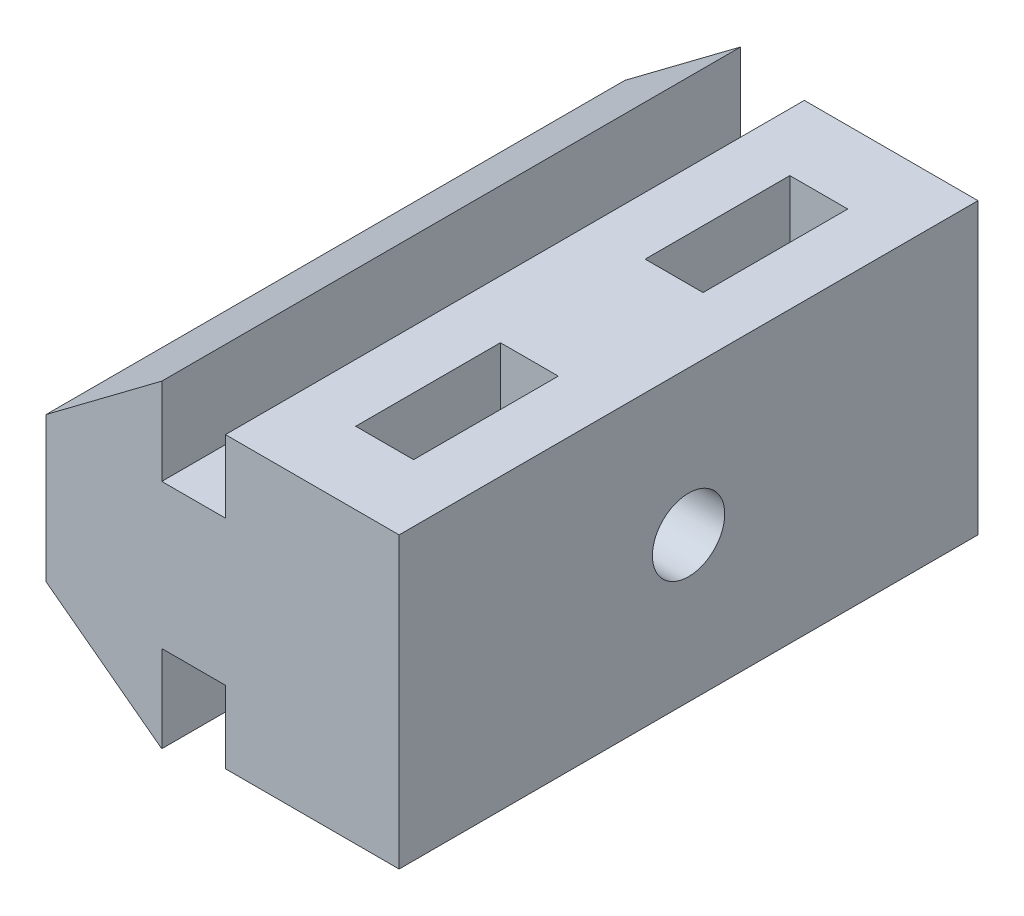
SolidWorks part; units mm, degrees
ref_plane "Plan de face" through (0, 0, 0) normal (0, 0, 1) x (1, 0, 0)
ref_plane "Plan de dessus" through (0, 0, 0) normal (0, 1, 0) x (1, 0, 0)
ref_plane "Plan de droite" through (0, 0, 0) normal (1, 0, 0) x (0, 0, -1)
sketch "ProfileRainureEsquisse" plane through (0, 0, 0) normal (0, 0, 1) x (1, 0, 0)
  line L0 (0, 0) -> (0, 5)
  line L1 (0, 5) -> (4, 8)
  line L2 (0, 0) -> (4, -3)
  line L3 (4, 8) -> (4, 5)
  line L4 (4, 5) -> (6.2, 5)
  line L5 (6.2, 0) -> (6.2, -2.5)
  line L6 (6.2, 0) -> (4, 0)
  line L7 (4, 0) -> (4, -3)
  line L8 (6.2, 5) -> (6.2, 7.5)
  line L9 (6.2, 7.5) -> (12.2, 7.5)
  line L10 (6.2, -2.5) -> (12.2, -2.5)
  line L11 (12.2, -2.5) -> (12.2, 7.5)
  point P4 (0, 2.5)
  point P14 (12.2, 2.5)
  dimension "D1" = 4
  dimension "D2" = 2.2
  dimension "D3" = 5
  dimension "D4" = 8
  dimension "D5" = 6
  dimension "D6" = 10
extrude "Boss.-Extru.1" add sketch "ProfileRainureEsquisse" along normal blind 20
sketch "Esquisse1" plane through (12.2, 0, 0) normal (1, 0, 0) x (0, 0, -1)
  line L0 (-20, 7.5) -> (0, 7.5) construction
  line L1 (-20, -2.5) -> (-20, 7.5) construction
  circle A0 centre (-10, 2.5) radius 1.25
  point P2 (-10, 7.5)
  point P3 (-20, 2.5)
  dimension "D1" = 2.5
extrude "Enlèv. mat.-Extru.1" cut sketch "Esquisse1" against normal through all
sketch "Esquisse2" plane through (0, 7.5, 0) normal (0, 1, 0) x (1, 0, 0)
  line L0 (12.2, 0) -> (6.2, 0) construction
  line L1 (12.2, -20) -> (6.2, -20) construction
  line L2 (6.2, -20) -> (6.2, 0) construction
  line L3 (8.2, -12.5) -> (10.2, -12.5)
  line L4 (8.2, -12.5) -> (8.2, -17.5)
  line L5 (8.2, -17.5) -> (10.2, -17.5)
  line L6 (10.2, -12.5) -> (10.2, -17.5)
  line L8 (8.2, -2.5) -> (10.2, -2.5)
  line L9 (8.2, -2.5) -> (8.2, -7.5)
  line L10 (8.2, -7.5) -> (10.2, -7.5)
  line L11 (10.2, -2.5) -> (10.2, -7.5)
  point P2 (9.2, 0)
  point P7 (9.2, -20)
  dimension "D1" = 5
  dimension "D3" = 2.5
  dimension "D2" = 2
  dimension "D4" = 2
  dimension "D5" = 2.5
extrude "Enlèv. mat.-Extru.2" cut sketch "Esquisse2" against normal through all
